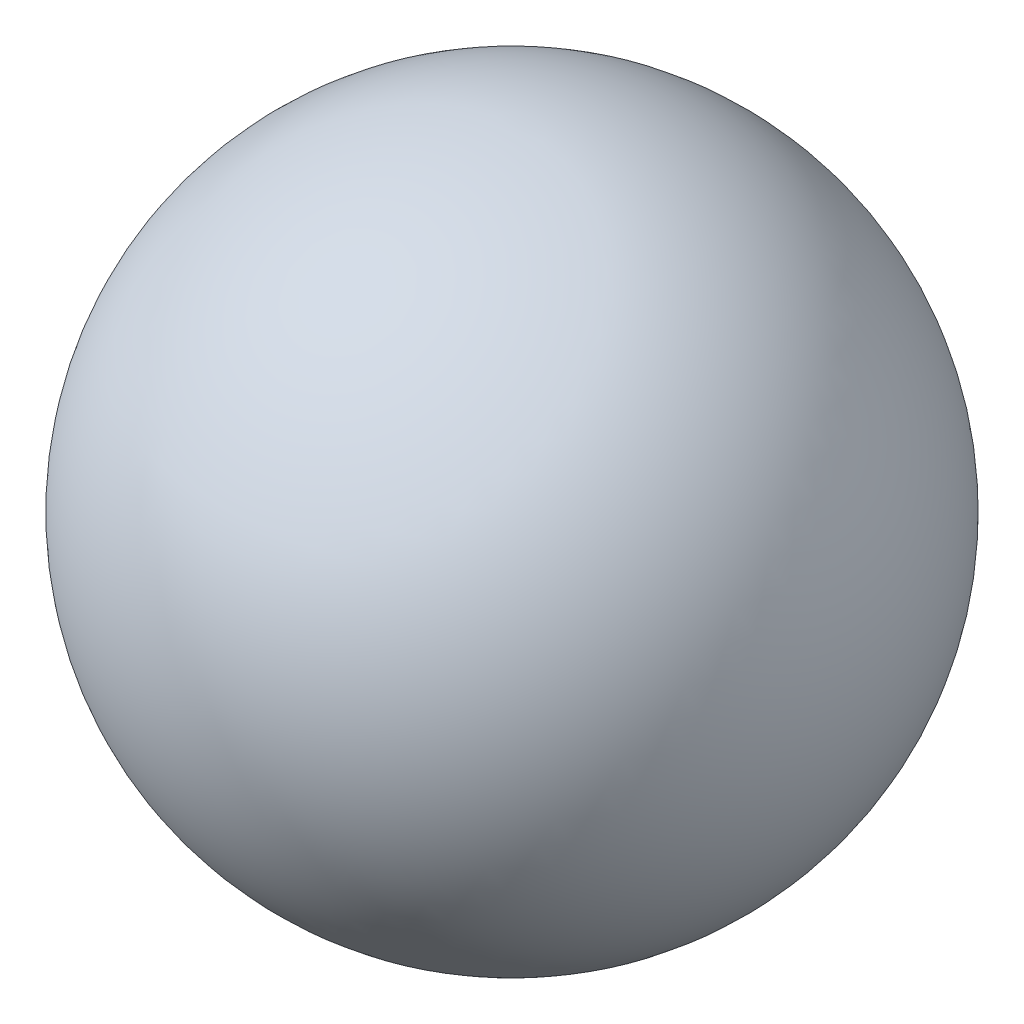
SolidWorks part; units mm, degrees
ref_plane "Front Plane" through (0, 0, 0) normal (0, 0, 1) x (1, 0, 0)
ref_plane "Top Plane" through (0, 0, 0) normal (0, 1, 0) x (1, 0, 0)
ref_plane "Right Plane" through (0, 0, 0) normal (1, 0, 0) x (0, 0, -1)
ref_axis "Axis1" through (0, -11, 0) along (0, 1, 0)
sketch "Sketch2" plane through (0, 0, 0) normal (0, 0, 1) x (1, 0, 0)
  line L0 (0, -11) -> (0, 11) construction
  line L1 (0, 11) -> (0, -11)
  arc A0 (0, 11) -> (0, -11) centre (0, 0) ccw
  dimension "D1" = 11
revolve "Revolve2" add sketch "Sketch2" angle 360 about axis through (0, -11, 0) along (0, 1, 0)
equation "\"radius\"=11"
equation "\"D1@Sketch2\"=\"radius\""
